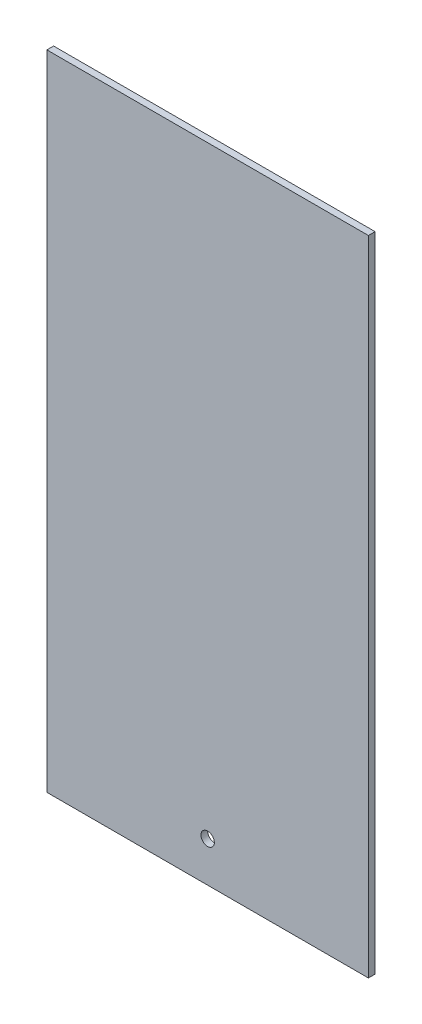
SolidWorks part; units mm, degrees
ref_plane "Front Plane" through (0, 0, 0) normal (0, 0, 1) x (1, 0, 0)
ref_plane "Top Plane" through (0, 0, 0) normal (0, 1, 0) x (1, 0, 0)
ref_plane "Right Plane" through (0, 0, 0) normal (1, 0, 0) x (0, 0, -1)
sketch "Sketch1" plane through (0, 0, 0) normal (0, 0, 1) x (1, 0, 0)
  line L1 (-76.2, -152.4) -> (76.2, -152.4)
  line L2 (-76.2, -152.4) -> (-76.2, 152.4)
  line L3 (-76.2, 152.4) -> (76.2, 152.4)
  line L4 (76.2, -152.4) -> (76.2, 152.4)
  line L5 (-76.2, -152.4) -> (76.2, 152.4) construction
  line L6 (-76.2, 152.4) -> (76.2, -152.4) construction
  point P0 (0, 0)
  dimension "D1" = 152.4
  dimension "D2" = 304.8
extrude "Boss-Extrude1" add sketch "Sketch1" along normal blind 3.175
sketch "Sketch2" plane through (0, 0, 3.175) normal (0, 0, 1) x (1, 0, 0)
  line L0 (-76.2, -152.4) -> (76.2, -152.4) construction
  circle A0 centre (0, -133.35) radius 3.175
  dimension "D1" = 6.35
  dimension "D2" = 19.05
extrude "Cut-Extrude1" cut sketch "Sketch2" against normal through all
